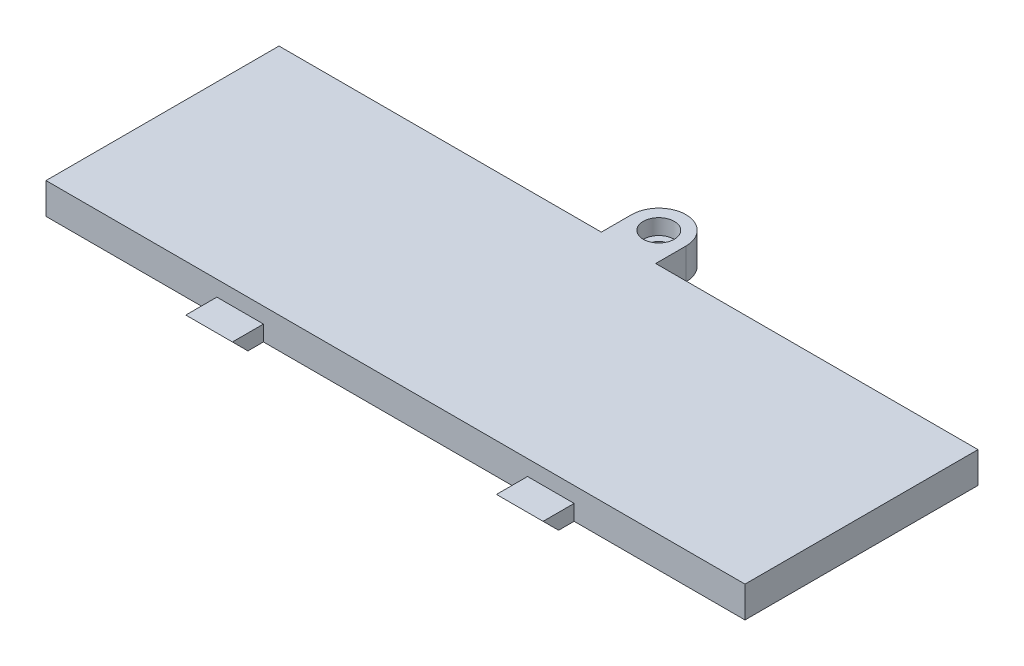
SolidWorks part; units mm, degrees
ref_plane "Front Plane" through (0, 0, 0) normal (0, 0, 1) x (1, 0, 0)
ref_plane "Top Plane" through (0, 0, 0) normal (0, 1, 0) x (1, 0, 0)
ref_plane "Right Plane" through (0, 0, 0) normal (1, 0, 0) x (0, 0, -1)
sketch "Sketch1" plane through (0, 0, 0) normal (0, 1, 0) x (1, 0, 0)
  line L1 (-45, 15) -> (45, 15)
  line L2 (-45, 15) -> (-45, -15)
  line L3 (-45, -15) -> (45, -15)
  line L4 (45, 15) -> (45, -15)
  line L9 (-3.5, 18.9) -> (3.5, 18.9)
  line L10 (-3.5, 18.9) -> (-3.5, 15)
  line L11 (-3.5, 15) -> (3.5, 15)
  line L12 (3.5, 18.9) -> (3.5, 15)
  circle A1 centre (0, 18.9) radius 3.5
  point P4 (0, 15)
  point P6 (-45, 0)
  dimension "D3" = 33.9
  dimension "D4" = 7
  dimension "D1" = 90
  dimension "D2" = 30
extrude "Boss-Extrude1" add sketch "Sketch1" along normal blind 4 contours L4 L1 L2 L3 | L1 | L10 L9 L12 L11 | A1 region at (0, 0, 0) region at (-3.4199, 0, -16.95)
sketch "Sketch4" plane through (0, 0, 15) normal (0, 0, 1) x (1, 0, 0)
  line L0 (-45, 0) -> (45, 0) construction
  line L1 (-23, 0) -> (-17, 0)
  line L2 (-23, 0) -> (-23, 2)
  line L3 (-23, 2) -> (-17, 2)
  line L4 (-17, 0) -> (-17, 2)
  line L5 (0, 4) -> (0, 0) construction
  line L6 (-45, 4) -> (45, 4) construction
  line L7 (23, 2) -> (17, 2)
  line L8 (17, 0) -> (17, 2)
  line L9 (23, 0) -> (17, 0)
  line L10 (23, 0) -> (23, 2)
  point P11 (-20, 0)
  dimension "D1" = 2
  dimension "D2" = 6
  dimension "D3" = 20
extrude "Boss-Extrude2" add sketch "Sketch4" along normal blind 4
chamfer "Chamfer1" distance 2 angle 45 2 edges at (20, 0, 19) (-20, 0, 19)
sketch "Sketch5" plane through (0, 4, 0) normal (0, 1, 0) x (1, 0, 0)
  circle A0 centre (0, 18.9) radius 1.1
  dimension "D1" = 2.2
extrude "Cut-Extrude1" cut sketch "Sketch5" against normal up to next
sketch "Sketch6" plane through (0, 4, 0) normal (0, 1, 0) x (1, 0, 0)
  circle A0 centre (0, 18.9) radius 2
  dimension "D1" = 4
extrude "Cut-Extrude2" cut sketch "Sketch6" against normal blind 2
